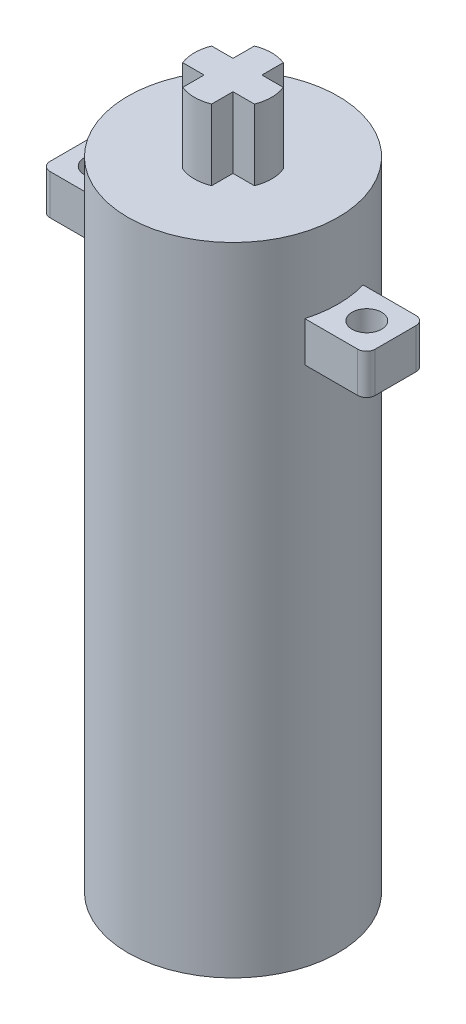
SolidWorks part; units mm, degrees
material "Plain Carbon Steel"
ref_plane "Front Plane" through (0, 0, 0) normal (0, 0, 1) x (1, 0, 0)
ref_plane "Top Plane" through (0, 0, 0) normal (0, 1, 0) x (1, 0, 0)
ref_plane "Right Plane" through (0, 0, 0) normal (1, 0, 0) x (0, 0, -1)
sketch "VigorSketch" plane through (0, 0, 0) normal (0, 1, 0) x (1, 0, 0)
  line L0 (0, -1.665) -> (0, 1.665)
  line L1 (-8.785, 1.665) -> (8.785, 1.665)
  line L2 (-9.285, 1.165) -> (-9.285, -1.165)
  line L3 (-8.785, -1.665) -> (8.785, -1.665)
  line L4 (9.285, 1.165) -> (9.285, -1.165)
  line L5 (2.0449, 0.8249) -> (0.8249, 0.8249)
  line L6 (0.8249, 0.8249) -> (0.8249, 2.0449)
  line L7 (-0.8249, 2.0449) -> (-0.8249, 0.8249)
  line L8 (-0.8249, 0.8249) -> (-2.0449, 0.8249)
  line L9 (-2.0449, -0.8249) -> (-0.8249, -0.8249)
  line L10 (-0.8249, -0.8249) -> (-0.8249, -2.0449)
  line L11 (2.0449, -0.8249) -> (0.8249, -0.8249)
  line L12 (0.8249, -0.8249) -> (0.8249, -2.0449)
  circle A0 centre (0, 0) radius 6
  arc A1 (-8.785, -1.665) -> (-9.285, -1.165) centre (-8.785, -1.165) cw
  arc A2 (9.285, -1.165) -> (8.785, -1.665) centre (8.785, -1.165) cw
  arc A3 (9.285, 1.165) -> (8.785, 1.665) centre (8.785, 1.165) ccw
  arc A4 (-8.785, 1.665) -> (-9.285, 1.165) centre (-8.785, 1.165) ccw
  circle A5 centre (7.6425, 0) radius 0.845
  circle A6 centre (-7.6425, 0) radius 0.845
  circle A7 centre (0, 0) radius 2.205
  point P7 (-9.285, 0)
  point P8 (9.285, 0)
  point P9 (0, 1.665)
  point P10 (0, -1.665)
  point P15 (9.285, -1.665)
  point P18 (9.285, 1.665)
  point P21 (-9.285, 1.665)
  point P40 (6, 0)
  dimension "D1" = 12
  dimension "D4" = 0.5
  dimension "D5" = 1.69
  dimension "D8" = 4.41
  dimension "D2" = 18.57
  dimension "D3" = 3.33
  dimension "D6" = 1.6425
  dimension "D7" = 1.665
  dimension "D9" = 1.22
extrude "VigorFlange" add sketch "VigorSketch" along normal blind 2.29 contours L1 A4 L2 A1 L3 A0 A6 | L1 A0 L3 L0 | L3 A0 L1 L0 | L4 A3 L1 A0 L3 A2 A5 region at (-3.9418, 0, 0) region at (3.9418, 0, 0) region at (-7.2747, 0, 1.6165) region at (5.9888, 0, 0.8476)
extrude "VigorAxle" add sketch "Sketch1<7>" along normal blind 10.62 contours L11 A7 L5 L6 L1 L0 L3 L12 | L8 A7 L9 L10 L3 L0 L1 L7 | L6 A7 L7 L1 | L10 A7 L12 L3 region at (-0.8902, 0, 0) region at (0, 0, 1.911) region at (0.8902, 0, 0) region at (0, 0, -1.911)
sketch "Sketch1<7>" plane through (0, 0, 0) normal (0, 1, 0) x (1, 0, 0) same geometry as "VigorSketch"
extrude "VigorBody" add sketch "VigorSketch<8>" along normal blind 6.58 and the other way blind 29.7899 contours A7 L1 A0 | A7 L3 A0 | L9 A7 L3 L10 | L1 A7 L8 L7 | L5 A7 L1 L6 | L3 A7 L11 L12 | L12 A7 L3 | L1 A7 L6 | L7 A7 L1 | L3 A7 L10 | A7 L1 A0 L3 | A7 L3 A0 L1 | L8 A7 L9 L10 L3 L0 L1 L7 | L11 A7 L5 L6 L1 L0 L3 L12 | L6 A7 L7 L1 | L10 A7 L12 L3 region at (-0.8902, 0, 0) region at (0, 0, 1.911) region at (0.8902, 0, 0) region at (0, 0, -1.911) region at (-1.044, 0, 1.7998) region at (-1.3254, 0, 1.2025) region at (1.3254, 0, 1.2025) region at (1.044, 0, 1.7998) region at (-1.3254, 0, -1.2025) region at (-1.044, 0, -1.7998) region at (1.044, 0, -1.7998) region at (1.3254, 0, -1.2025) region at (0, 0, 3.5146) region at (-3.9418, 0, 0) region at (3.9418, 0, 0) region at (0, 0, -3.5146)
sketch "VigorSketch<8>" plane through (0, 0, 0) normal (0, 1, 0) x (1, 0, 0) same geometry as "VigorSketch"
equation "\"vigorwidth\"= 0.472441in"
equation "\"D1@VigorSketch\"=\"vigorwidth\""
equation "\"vigorflangewidth\"= 0.731102in"
equation "\"D2@VigorSketch\"=\"vigorflangewidth\""
equation "\"vigorflangelength\"= 0.131102in"
equation "\"D3@VigorSketch\"=\"vigorflangelength\""
equation "\"vigorscrewsize\"= 0.066535in"
equation "\"D5@VigorSketch\"=\"vigorscrewsize\""
equation "\"vigorholeoffsetwid\"= 0.0646653in"
equation "\"D6@VigorSketch\"=\"vigorholeoffsetwid\""
equation "\"vigorholeoffsetlen\"= 0.065551in"
equation "\"D7@VigorSketch\"= \"vigorholeoffsetlen\""
equation "\"vigorflangedepth\"= 0.0901575in"
equation "\"vigordiscdepth\"= 0.0492126in"
equation "\"vigormotordepth\"= 1.12362in"
equation "\"vigortipdepth\"= 0.259055in"
equation "\"vigoraxlewidth\"= 0.173622in"
equation "\"D8@VigorSketch\"=\"vigoraxlewidth\""
equation "\"vigorcutlen\"= 0.0480315in"
equation "\"D9@VigorSketch\"=\"vigorcutlen\""
equation "\"vigoraxledepth\"= 0.159055in"
equation "\"D1@VigorBody\"=\"vigortipdepth\""
equation "\"D2@VigorBody\"=\"vigordiscdepth\"+\"vigormotordepth\""
equation "\"D1@VigorFlange\"=\"vigorflangedepth\""
equation "\"D1@VigorAxle\"=\"vigortipdepth\"+\"vigoraxledepth\""
equation "\"CageLeftBottomEdge\"=22.11mm"
equation "\"CageLeftTopEdge\"=22.11mm"
equation "\"CageRightBottomEdge\"=21.63mm"
equation "\"CageRightTopEdge\"=21.63mm"
equation "\"CageHeight\"=86.04mm"
equation "\"CageLength\"=73.76mm"
equation "\"CageTopScrewClearance\"=10mm"
equation "\"CageBottomScrewClearance\"=25mm"
equation "\"CageLeftTopDepth\"= 11.65mm"
equation "\"CageLeftBottomDepth\"=11.11mm"
equation "\"CageLeftTopHeight\"=8.56175mm"
equation "\"CageLeftBottomHeight\"=16mm"
equation "\"CageRightTopDepth\"= 11.05mm"
equation "\"CageRightBottomDepth\"=10.58mm"
equation "\"CageRightTopHeight\"=9.6mm"
equation "\"CageRightBottomHeight\"=15.49mm"
equation "\"CageLeftTopChannelDepth\"=2.41908mm"
equation "\"CageLeftBottomChannelDepth\"=2.588mm"
equation "\"CageLeftChannelHeight\"=11.7mm"
equation "\"CageRightTopChannelDepth\"=2.32mm"
equation "\"CageRightBottomChannelDepth\"=2.318mm"
equation "\"CageRightChannelHeight\"=10mm"
equation "\"CageChanRelHeight\"=23.99mm"
equation "\"CageChanRelDepth\"=5.492mm"
equation "\"CageChamberRadius\"=16.261mm"
equation "\"CageScrewDiameter\"=4.8mm"
equation "\"CageSetScrewDiameter\"=3.5mm"
equation "\"CageAxleRadius\"=6.639mm"
equation "\"CageAxleKeyHeight\"=1.619mm"
equation "\"CageAxleKeyWidth\"=2.662mm"
equation "\"CageHoseWindowWidth\"=16.29mm"
equation "\"CageHoseWindowHeight\"=26.5mm"
equation "\"CageHoseWindow-Edge\"=8.89mm"
equation "\"CageScrew-VerticalEdge\"=5.0mm"
equation "\"CageScrew-HorizontalEdge\"=7.5mm"
equation "\"CageScrew-HoseCornerScrewEdge\"=4.45mm"
equation "\"CageAxle-BottomEdge\"=56.05mm"
equation "\"CageAxle-FrontEdge\"=46.03mm"
equation "\"CageBackSetScrew-Axle\"=40mm"
equation "\"CageFrontSetScrew-Axle\"=22mm"
equation "\"CageVelocityWindow-BackEdge\"=34.8mm"
equation "\"CageVelocityWindow-BottomEdge\"=27.55mm"
equation "\"CageVelocityWindowHeight\"=22.29mm"
equation "\"CageVelocityWindowWidth\"=12.61mm"
equation "\"TriggerSlot-BottomEdge\"=6.35mm"
equation "\"TriggerSlot-FrontEdge\"=15mm"
equation "\"TriggerSlotSize\"=6.7mm"
equation "\"TriggerRackOffset\"=6mm"
equation "\"TriggerSlotSizeInt\"=.25in"
equation "\"MotorMountLegLength\"=.25in"
equation "\"GearOffset\"=.264907in"
equation "\"TriggerSlotSpacing\"=.25in"
equation "\"TriggerMiniSlotWidth\"=3.5mm"
equation "\"TriggerRackWidth\"=6.5mm"
equation "\"gearhubintdiam\"=30mm"
equation "\"gearhubintwid\"=15mm"
equation "\"pandiscradius\"=14in"
equation "\"towermaterialwidth\"=.25in"
equation "\"towerslotlength\"=.5in"
equation "\"towermarkerspace\"=5in"
equation "\"towerslothorizoffset\"=1in"
equation "\"towerslothorizspacing\"=2in"
equation "\"towerslotvertoffset\"=3in"
equation "\"towerslotvertspacing\"=1in"
equation "\"towerheight\"=12in"
equation "\"towerupslot\"=1in"
equation "\"toweraxle\"=.5in"
equation "\"towerspeedwidth\"=2in"
equation "\"towerspeedheight\"=8in"
equation "\"towerspeedgap\"=2in"
equation "\"stepperouterrad\"=10mm"
equation "\"stepperscrewsize\"=3.45mm"
equation "\"stepperscrewc2c\"=49.5mm"
equation "\"stepperdepthoffset\"=24mm"
equation "\"stepperhorizoffset\"=22.91mm"
equation "\"stepperaxleflat\"=.037in"
equation "\"stepperaxlerad\"=0.11811024in"
equation "\"shaftslotOD\"=18.8mm"
equation "\"shaftslotID\"=13.28mm"
equation "\"shaftkeywidth\"=2.67mm"
equation "\"shaftkeydepth\"=1.8mm"
equation "\"shaftcollartotaldepth\"=12.5mm"
equation "\"shaftsquaredepth\"=6mm"
equation "\"shaftsetscrewsize\"=3.5mm"
equation "\"shaftkeytightdepth\"=1.85mm"
equation "\"shaftslottightID\"=12.78mm"
equation "\"shaftsetscrewoffset\"=9mm"
equation "\"cagecollartotaldepth\"=10mm"
equation "\"cagecollartotalwidth\"=35mm"
equation "\"cagecollarbasedepth\"=4mm"
equation "\"ajaxaxlesize\"=3.87mm"
equation "\"ajaxinnercut\"=2.3mm"
equation "\"ajaxwidth\"=6.1mm"
equation "\"ajaxdiametral\"=25.8854"
equation "\"ajaxcutoutdepth\"=2.3mm"
equation "\"ajax4020gap\"=29.5mm"
equation "\"ajax4010gap\"=24.5mm"
equation "\"ajax20hubbuffer\"=6.1mm"
equation "\"ajax20hubholeoffset\"=.19685in"
equation "\"ajax20hubholesize\"=.059055in"
equation "\"ajax20cutoutint\"=13.4mm"
equation "\"ajax40hubholesize\"=7.21mm"
equation "\"ajax40hubholeoffset\"=10mm"
equation "\"ajax40hubbuffer\"=8.9mm"
equation "\"ajax40cutoutint\"=32.6mm"
equation "\"bearingpandiscrad\"=6.8in"
equation "\"bearingpandiscang\"=48.75deg"
equation "\"bearingclearholedist\"=4.7345in"
equation "\"bearingclearholesize\"=.5in"
equation "\"bearingclearholeang\"=22.5deg"
equation "\"bearingmountholedist\"=4.25in"
equation "\"bearingwirehole\"=1.5in"
equation "\"no6diam\"=.146in"
equation "\"shortconangle\"=20deg"
equation "\"shortconlen\"=.875in"
equation "\"longconlen\"=1.25in"
equation "\"longconangle\"=15deg"
